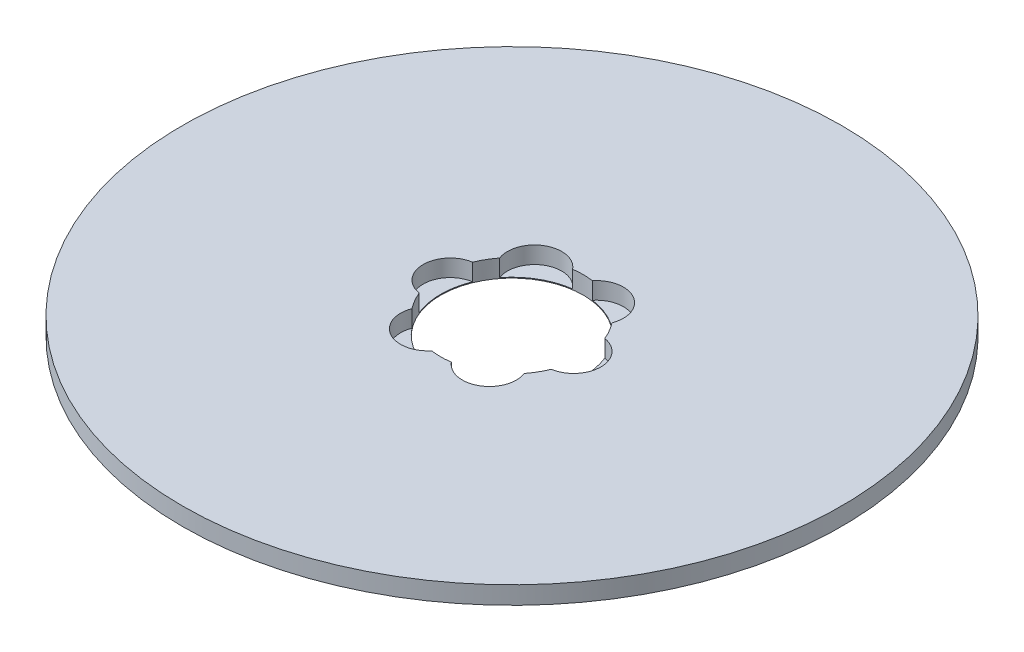
SolidWorks part; units mm, degrees
ref_plane "Front Plane" through (0, 0, 0) normal (0, 0, 1) x (1, 0, 0)
ref_plane "Top Plane" through (0, 0, 0) normal (0, 1, 0) x (1, 0, 0)
ref_plane "Right Plane" through (0, 0, 0) normal (1, 0, 0) x (0, 0, -1)
sketch "Sketch1" plane through (0, 0, 0) normal (0, 1, 0) x (1, 0, 0)
  circle A0 centre (0, 0) radius 92.5
  dimension "FLANGE_OD" = 185
extrude "Boss-Extrude1" add sketch "Sketch1" along normal blind 5
sketch "Sketch2" plane through (0, 0, 0) normal (0, 1, 0) x (1, 0, 0)
  circle A0 centre (0, 0) radius 20
  dimension "BORE_D" = 40
extrude "Cut-Extrude1" cut sketch "Sketch2" along normal through all
sketch "Sketch3" plane through (0, 5, 0) normal (0, 1, 0) x (1, 0, 0)
  circle A0 centre (0, 0) radius 17.3303 construction
  circle A1 centre (-17.3303, 0) radius 7.5961
  dimension "BOLT_D" = 15.1923
  dimension "BOLT_PCD" = 34.6605
extrude "Cut-Extrude2" cut sketch "Sketch3" against normal blind 4.7699
pattern_circular "CirPattern1" count 6 over 360 about axis through (0, 0, 0) along (0, 1, 0) of "Cut-Extrude2"
